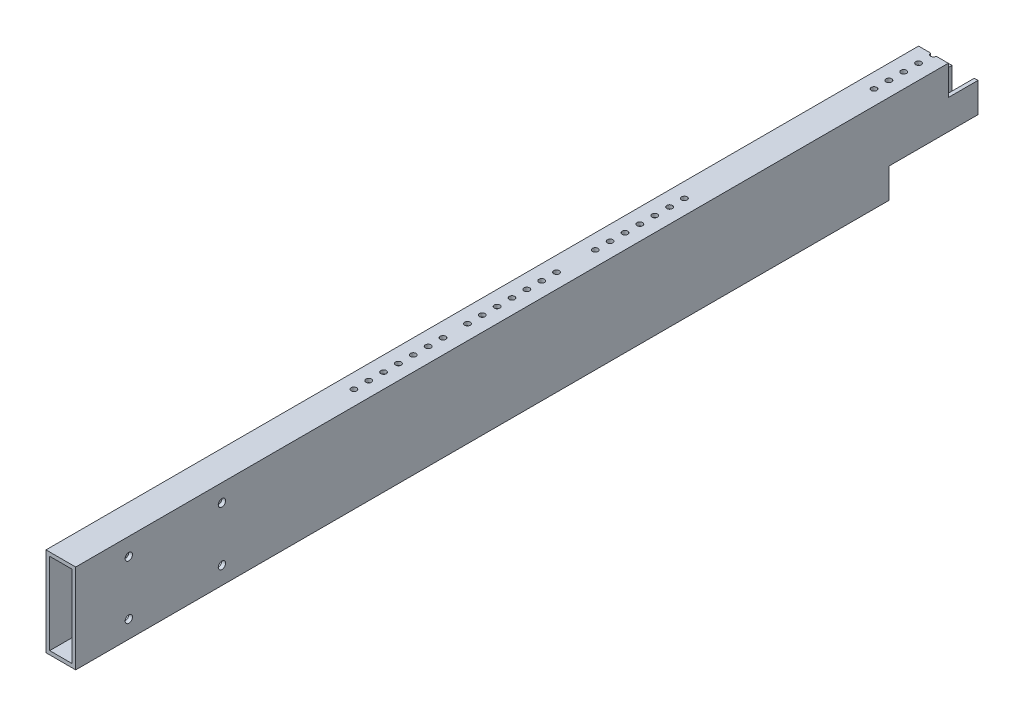
SolidWorks part; units mm, degrees
ref_plane "Front Plane" through (0, 0, 0) normal (0, 0, 1) x (1, 0, 0)
ref_plane "Top Plane" through (0, 0, 0) normal (0, 1, 0) x (1, 0, 0)
ref_plane "Right Plane" through (0, 0, 0) normal (1, 0, 0) x (0, 0, -1)
sketch "Sketch1" plane through (0, 0, 0) normal (0, 0, 1) x (1, 0, 0)
  line L1 (-12.7, -38.1) -> (12.7, -38.1)
  line L2 (-12.7, -38.1) -> (-12.7, 38.1)
  line L3 (-12.7, 38.1) -> (12.7, 38.1)
  line L4 (12.7, -38.1) -> (12.7, 38.1)
  line L5 (-12.7, -38.1) -> (12.7, 38.1) construction
  line L6 (-12.7, 38.1) -> (12.7, -38.1) construction
  point P0 (0, 0)
  dimension "D1" = 25.4
  dimension "D2" = 76.2
extrude "Boss-Extrude1" add sketch "Sketch1" along normal mid plane 771.398
shell "Shell1" thickness 3.175 removed face at (0, 0, -385.699) removed face at (0, 0, 385.699)
sketch "Sketch2" plane through (12.7, 0, 0) normal (1, 0, 0) x (0, 0, -1)
  line L1 (385.699, -38.1) -> (309.499, -38.1)
  line L2 (385.699, -38.1) -> (385.699, -12.7)
  line L3 (385.699, -12.7) -> (309.499, -12.7)
  line L4 (309.499, -38.1) -> (309.499, -12.7)
  dimension "D1" = 25.4
  dimension "D2" = 76.2
extrude "Cut-Extrude1" cut sketch "Sketch2" against normal through all
sketch "Sketch3" plane through (12.7, 0, 0) normal (1, 0, 0) x (0, 0, -1)
  line L1 (385.699, 38.1) -> (360.299, 38.1)
  line L2 (385.699, 38.1) -> (385.699, 12.7)
  line L3 (385.699, 12.7) -> (360.299, 12.7)
  line L4 (360.299, 38.1) -> (360.299, 12.7)
  dimension "D1" = 25.4
extrude "Cut-Extrude2" cut sketch "Sketch3" against normal through all
sketch "Sketch4" plane through (0, 38.1, 0) normal (0, 1, 0) x (1, 0, 0)
  line L0 (-12.7, 360.299) -> (12.7, 360.299) construction
  circle A0 centre (0, 147.3945) radius 2.3812
  circle A1 centre (0, 134.6945) radius 2.3812
  circle A2 centre (0, 121.9945) radius 2.3812
  circle A3 centre (0, 109.2945) radius 2.3812
  circle A4 centre (0, 96.5945) radius 2.3812
  circle A5 centre (0, 83.8945) radius 2.3812
  circle A6 centre (0, 71.1945) radius 2.3812
  circle A7 centre (0, 38.0987) radius 2.3812
  circle A8 centre (0, 25.3987) radius 2.3813
  circle A9 centre (0, 12.6987) radius 2.3813
  circle A10 centre (0, -0.0013) radius 2.3813
  circle A11 centre (0, -12.7013) radius 2.3812
  circle A12 centre (0, -25.4013) radius 2.3812
  circle A13 centre (0, -38.1013) radius 2.3812
  circle A15 centre (0, -58.9932) radius 2.3812
  circle A16 centre (0, -71.6932) radius 2.3812
  circle A17 centre (0, -84.3932) radius 2.3812
  circle A18 centre (0, -97.0932) radius 2.3812
  circle A19 centre (0, -109.7932) radius 2.3812
  circle A20 centre (0, -122.4932) radius 2.3812
  circle A21 centre (0, -135.1932) radius 2.3813
  point P33 (0, 360.299)
  dimension "D1" = 4.7625
  dimension "D3" = 12.7
  dimension "D4" = 12.7
  dimension "D5" = 12.7
  dimension "D6" = 12.7
  dimension "D7" = 12.7
  dimension "D8" = 12.7
  dimension "D9" = 322.2003
  dimension "D10" = 12.7
  dimension "D11" = 12.7
  dimension "D12" = 12.7
  dimension "D13" = 12.7
  dimension "D14" = 12.7
  dimension "D15" = 12.7
  dimension "D16" = 12.7
  dimension "D17" = 419.2922
  dimension "D18" = 12.7
  dimension "D19" = 12.7
  dimension "D20" = 12.7
  dimension "D21" = 12.7
  dimension "D22" = 12.7
  dimension "D2" = 212.9045
extrude "Cut-Extrude3" cut sketch "Sketch4" against normal through all
sketch "Sketch5" plane through (0, 38.1, 0) normal (0, 1, 0) x (1, 0, 0)
  line L0 (-12.7, 360.299) -> (12.7, 360.299) construction
  circle A0 centre (0, 360.299) radius 2.3813
  circle A1 centre (0, 347.599) radius 2.3813
  circle A2 centre (0, 334.899) radius 2.3813
  circle A3 centre (0, 322.199) radius 2.3813
  circle A4 centre (0, 309.499) radius 2.3813
  dimension "D1" = 4.7625
  dimension "D3" = 12.7
  dimension "D4" = 12.7
  dimension "D5" = 12.7
  dimension "D8" = 0
  dimension "D2" = 12.7
extrude "Cut-Extrude4" cut sketch "Sketch5" against normal up to next
sketch "Sketch6" plane through (0, -38.1, 0) normal (0, -1, 0) x (1, 0, 0)
  line L0 (-12.7, -309.499) -> (12.7, -309.499) construction
  circle A0 centre (0, -309.499) radius 2.3813
  circle A1 centre (0, -296.799) radius 2.3813
  circle A2 centre (0, -284.099) radius 2.3813
  circle A3 centre (0, -258.699) radius 2.3813
  circle A6 centre (0, -271.399) radius 2.3813
  dimension "D1" = 4.7625
  dimension "D2" = 12.7
  dimension "D3" = 12.7
  dimension "D4" = 12.7
  dimension "D5" = 12.7
  dimension "D6" = 0
extrude "Cut-Extrude5" cut sketch "Sketch6" against normal up to next
sketch3d "3DSketch1" [suppressed]
  line L0 (0, 34.925, -109.2945) -> (0, 38.1, -109.2945) construction
  line L1 (0, 34.925, 97.0932) -> (0, 38.1, 97.0932) construction
  point P0 (0, 38.1, -109.2945)
  point P1 (0, 0, 0)
  point P4 (0, 38.1, 97.0932)
sketch "Sketch11" plane through (12.7, 0, 0) normal (1, 0, 0) x (0, 0, -1)
  point P0 (-340.299, 23.1254)
  point P1 (-260.699, 23.1254)
  point P3 (-260.699, -23.1)
  point P5 (-340.299, -23.1)
hole_wizard "CBORE for M6 Hex Head Bolt1" positions "Sketch19" profile "Sketch18" counterbore size "M6" standard "Lanco STD" end condition through all
sketch "Sketch19" plane through (-12.7, 0, 0) normal (-1, 0, 0) x (0, 0, 1)
  point P0 (260.699, 23.1254)
  point P3 (260.699, -23.1)
  point P6 (340.299, 23.1254)
  point P9 (340.299, -23.1)
sketch "Sketch18" plane through (-12.7, 23.1254, 260.699) normal (0, 1, 0) x (0, 0, 1)
  line L0 (0, 0) -> (0, 25.4)
  line L1 (0, 25.4) -> (3.15, 25.4)
  line L3 (3.15, 25.4) -> (3.15, 4)
  line L4 (3.15, 4) -> (7.2735, 4)
  line L5 (7.2735, 4) -> (7.2735, 0)
  line L7 (7.2735, 0) -> (0, 0)
  line L11 (0, -6.35) -> (0, 107.95) construction
  dimension "Thru Hole Dia." = 6.3
  dimension "Thru Hole Depth" = 25.4
  dimension "C'Bore Dia." = 14.547
  dimension "C'Bore Depth" = 4
